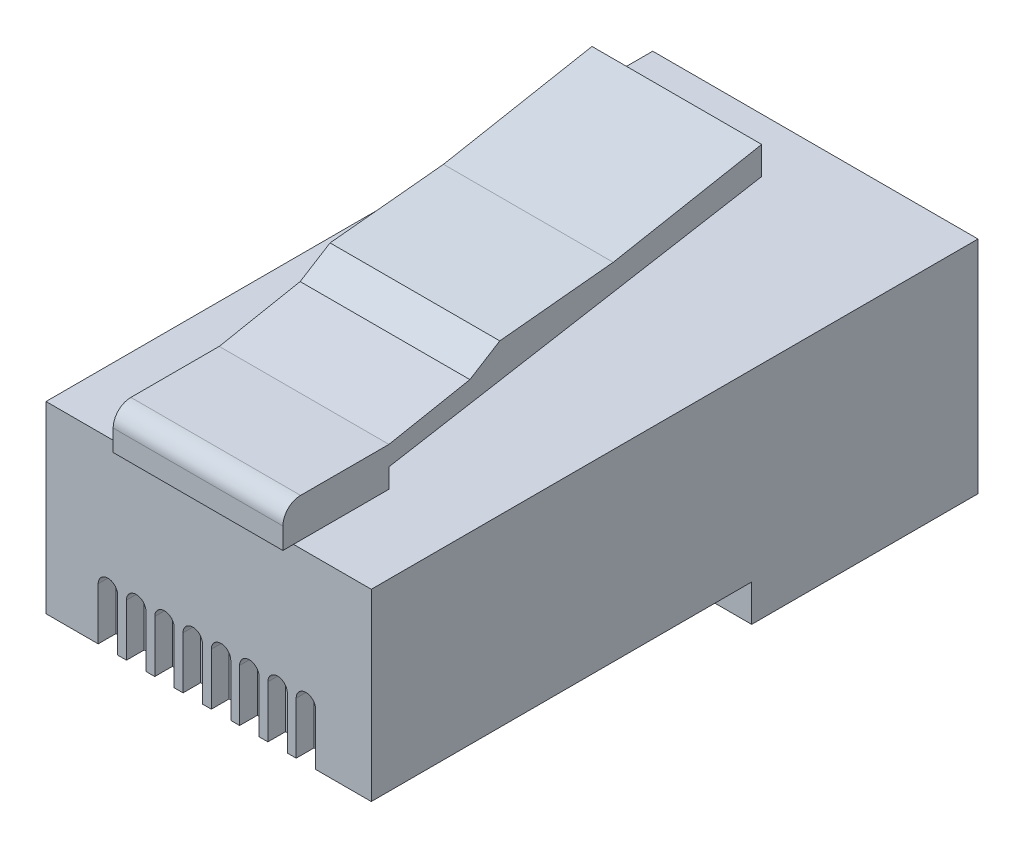
SolidWorks part; units mm, degrees
ref_plane "Plane1" through (0, 0, 0) normal (0, 0, 1) x (1, 0, 0)
ref_plane "Plane2" through (0, 0, 0) normal (0, 1, 0) x (1, 0, 0)
ref_plane "Plane3" through (0, 0, 0) normal (1, 0, 0) x (0, 0, -1)
sketch "Sketch1" plane through (0, 0, 0) normal (0, 0, 1) x (1, 0, 0)
  line L0 (-5.842, 3.302) -> (5.842, 3.302)
  line L1 (-5.842, 3.302) -> (-5.842, -3.302)
  line L2 (-5.842, -3.302) -> (5.842, -3.302)
  line L3 (5.842, 3.302) -> (5.842, -3.302)
  line L4 (-5.842, 3.302) -> (5.842, -3.302) construction
  dimension "D1" = 11.684
  dimension "D2" = 6.604
extrude "Base-Extrude" add sketch "Sketch1" along normal blind 21.7932
sketch "Sketch2" plane through (0, -3.302, 0) normal (0, -1, 0) x (1, 0, 0)
  line L0 (5.842, 21.7932) -> (5.842, 0) construction
  line L1 (-5.842, 0) -> (5.842, 0)
  line L2 (-5.842, 0) -> (-5.842, 8.1299)
  line L3 (-5.842, 8.1299) -> (5.842, 8.1299)
  line L4 (5.842, 0) -> (5.842, 8.1299)
extrude "Boss-Extrude1" add sketch "Sketch2" along normal blind 1.3208
sketch "Sketch4" plane through (0, 3.302, 0) normal (0, 1, 0) x (-1, 0, 0)
  line L0 (-3.048, 18.3642) -> (-3.048, 22.1742)
  line L2 (-3.048, 18.3642) -> (3.048, 18.3642)
  line L4 (3.048, 18.3642) -> (3.048, 22.1742)
  line L5 (-3.048, 22.1742) -> (3.048, 22.1742)
  line L7 (-5.842, 21.7932) -> (-5.842, 0) construction
  line L8 (-5.842, 21.7932) -> (5.842, 21.7932) construction
  dimension "D1" = 2.794
  dimension "D2" = 3.429
  dimension "D3" = 6.096
  dimension "D4" = 3.81
extrude "Boss-Extrude3" add sketch "Sketch4" along normal blind 1.397
fillet "Fillet5" radius 0.635 1 edges at (0, 4.699, 22.1742)
sketch "Sketch6" plane through (0, 0, 21.7932) normal (0, 0, 1) x (1, 0, 0)
  line L0 (3.843, -1.43) -> (3.843, -3.302)
  line L2 (5.2997, -1.43) -> (1.8337, -1.43) construction
  line L4 (3.1445, -3.302) -> (3.1445, -1.43)
  line L5 (3.1445, -3.302) -> (3.843, -3.302)
  line L6 (-5.842, -3.302) -> (5.842, -3.302) construction
  line L7 (5.842, -3.302) -> (5.842, 3.302) construction
  arc A0 (3.1445, -1.43) -> (3.843, -1.43) centre (3.4938, -1.43) cw
  dimension "D1" = 1.999
  dimension "D2" = 1.872
  dimension "D3" = 0.6985
extrude "Cut-Extrude2" cut sketch "Sketch6" against normal blind 4.318
sketch "Sketch24" plane through (0, 0, 17.4752) normal (0, 0, 1) x (1, 0, 0)
  line L0 (3.2715, -3.175) -> (3.716, -3.175)
  line L1 (3.716, -3.175) -> (3.716, -1.1606)
  line L2 (3.1445, -1.43) -> (3.1445, -3.302) construction
  line L3 (3.2715, -3.175) -> (3.2715, -1.1606)
  line L4 (3.843, -3.302) -> (3.843, -1.43) construction
  line L6 (3.843, -3.302) -> (3.1445, -3.302) construction
  arc A1 (3.843, -1.43) -> (3.1445, -1.43) centre (3.4938, -1.43) ccw construction
  arc A2 (3.716, -1.1606) -> (3.2715, -1.1606) centre (3.4938, -1.43) ccw
  dimension "D1" = 0.127
  dimension "D2" = 0.127
  dimension "D3" = 0.127
extrude "Extrude1" add sketch "Sketch24" along normal offset from surface (3.81 mm away) 0.508 up to face at (1.3975, -0.2511, 21.7932)
fillet "Fillet6" [suppressed] radius 0.381
pattern_linear "LPattern4" count 8 spacing 1.016 along (-1, 0, 0) of "Cut-Extrude2", "Extrude1"
sketch "Sketch10" plane through (3.048, 0, 0) normal (1, 0, 0) x (0, 0, -1)
  line L0 (-18.3642, 4.699) -> (-4.9755, 4.699) construction
  line L1 (-18.3642, 4.0005) -> (-4.9755, 6.3349)
  line L2 (-18.3642, 4.699) -> (-18.3642, 3.302) construction
  line L3 (-4.9755, 6.3349) -> (-4.9755, 7.3349)
  line L4 (-4.9755, 7.3349) -> (-10.3093, 6.3349)
  line L5 (-10.3093, 6.3349) -> (-14.3836, 5.9274)
  line L6 (-14.3836, 5.9274) -> (-15.4578, 5.2607)
  line L7 (-15.4578, 5.2607) -> (-18.3642, 4.699)
  line L8 (-18.3642, 4.699) -> (-18.3642, 4.0005)
extrude "Boss-Extrude5" add sketch "Sketch10" against normal up to vertex (6.096 mm away) up to point (-3.048, 4.699, 18.3642)
sketch "Sketch12" [suppressed] plane through (0, 3.302, 0) normal (0, 1, 0) x (-1, 0, 0)
  line L0 (-1.4618, 17.4752) -> (-1.4618, 21.2852) construction
  line L1 (-3.048, 4.9755) -> (-1.4618, 4.9755)
  line L2 (-3.048, 4.9755) -> (-3.048, 14.2719)
  line L3 (-3.048, 14.2719) -> (-1.4618, 14.2719)
  line L4 (-1.4618, 4.9755) -> (-1.4618, 14.2719)
  line L5 (3.048, 10.3093) -> (3.048, 14.3836) construction
  line L6 (3.048, 4.9755) -> (3.048, 10.3093) construction
  line L7 (3.048, 10.3093) -> (3.048, 14.2719)
  line L8 (3.048, 4.9755) -> (3.048, 10.3093)
  line L9 (1.4732, 4.9755) -> (1.4732, 14.2719)
  line L10 (3.048, 4.9755) -> (-3.048, 4.9755) construction
  line L11 (3.048, 4.9755) -> (1.4732, 4.9755)
  line L12 (1.4732, 14.2719) -> (3.048, 14.2719)
  dimension "D1" = 1.5748
  dimension "D2" = 9.2964
extrude "Cut-Extrude5" [suppressed] cut sketch "Sketch12" along normal through all
sketch "Sketch13" plane through (0, -3.302, 0) normal (0, -1, 0) x (1, 0, 0)
  line L0 (0, 0) -> (0, 24.4214) construction
  line L1 (5.207, 16.7132) -> (5.207, 16.0782)
  line L2 (5.207, 16.7132) -> (-5.207, 16.7132)
  line L4 (5.207, 16.0782) -> (-5.207, 16.0782)
  line L5 (-5.207, 16.7132) -> (-5.207, 16.0782)
  line L7 (3.843, 21.7932) -> (5.842, 21.7932) construction
  dimension "D1" = 10.414
  dimension "D2" = 0.635
  dimension "D3" = 5.08
extrude "Cut-Extrude6" cut sketch "Sketch13" against normal blind 3.175
sketch "Sketch14" plane through (0, -3.302, 0) normal (0, -1, 0) x (1, 0, 0)
  line L0 (0, 0) -> (0, 24.9029) construction
  line L3 (-5.842, 21.7932) -> (-3.9675, 21.7932) construction
  line L6 (-4.0894, 10.4902) -> (4.0894, 10.4902)
  line L7 (-4.0894, 10.4902) -> (-4.0894, 13.7922)
  line L8 (-4.0894, 13.7922) -> (4.0894, 13.7922)
  line L9 (4.0894, 10.4902) -> (4.0894, 13.7922)
  dimension "D1" = 8.1788
  dimension "D2" = 3.302
  dimension "D3" = 8.001
extrude "Cut-Extrude7" cut sketch "Sketch14" against normal blind 1.5875
sketch "Sketch16" plane through (0, -4.6228, 0) normal (0, -1, 0) x (1, 0, 0)
  line L0 (0, 0) -> (0, 11.4945) construction
  line L1 (-4.0894, 6.35) -> (-4.0894, 2.54)
  line L3 (-5.842, 0) -> (5.842, 0) construction
  line L4 (-4.0894, 6.35) -> (4.0894, 6.35)
  line L6 (-4.0894, 2.54) -> (4.0894, 2.54)
  line L7 (4.0894, 6.35) -> (4.0894, 2.54)
  dimension "D1" = 8.1788
  dimension "D2" = 2.54
  dimension "D3" = 3.81
extrude "Cut-Extrude8" cut sketch "Sketch16" against normal blind 3.81
sketch "Sketch18" plane through (0, 0, 0) normal (0, 0, -1) x (-1, 0, 0)
  line L0 (-5.842, 3.302) -> (5.842, 3.302) construction
  line L2 (-4.0894, 1.4732) -> (-4.0894, -2.3876)
  line L3 (-4.0894, -2.3876) -> (4.0894, -2.3876)
  line L4 (4.0894, 1.4732) -> (4.0894, -2.3876)
  line L5 (0, 7.8284) -> (0, -5.1163) construction
  arc A0 (-4.0894, 1.4732) -> (4.0894, 1.4732) centre (0, -15.3376) cw
  dimension "D1" = 1.8288
  dimension "D2" = 3.8608
  dimension "D3" = 8.1788
extrude "Cut-Extrude10" cut sketch "Sketch18" against normal blind 15.24
sketch "Sketch25" plane through (0, 0, 15.24) normal (0, 0, -1) x (-1, 0, 0)
  line L0 (-4.0894, 1.4732) -> (4.0894, -2.3876) construction
  point P0 (0, -0.4572)
other "CPoint1" parameters "Diameter"=1, "StubLength"=20
ref_axis "Axis1" through (0, -0.4572, 5.24) along (0, 0, 1)
sketch "Sketch27" plane through (0, 0, 22.1742) normal (0, 0, 1) x (1, 0, 0)
  point P0 (0, 0)
